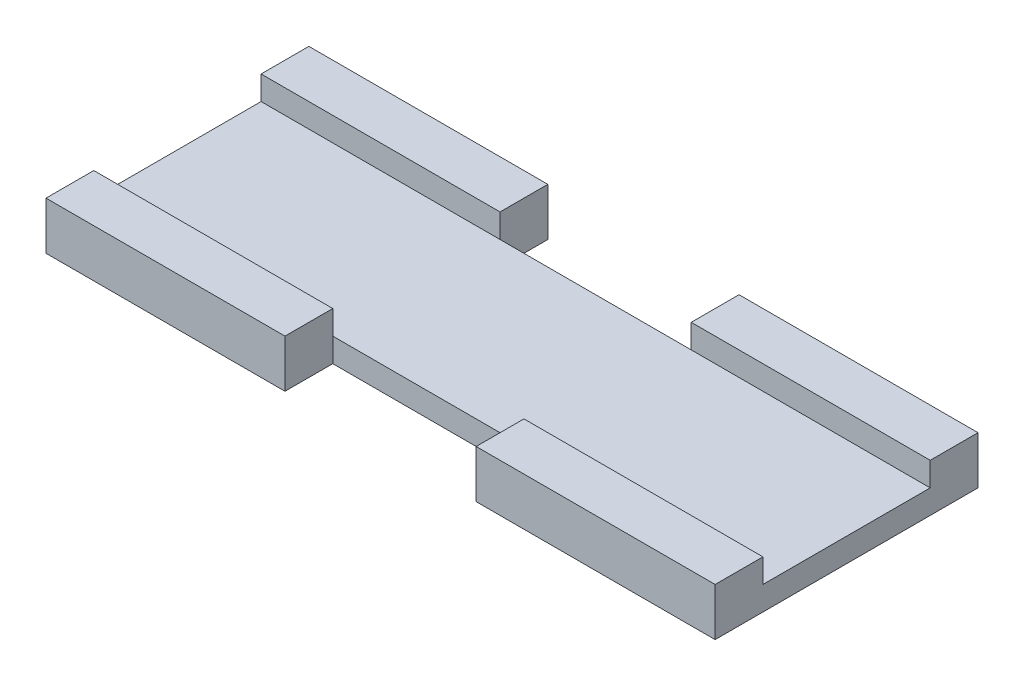
SolidWorks part; units mm, degrees
ref_plane "Спереди" through (0, 0, 0) normal (0, 0, 1) x (1, 0, 0)
ref_plane "Сверху" through (0, 0, 0) normal (0, 1, 0) x (1, 0, 0)
ref_plane "Справа" through (0, 0, 0) normal (1, 0, 0) x (0, 0, -1)
sketch "Эскиз1" plane through (0, 0, 0) normal (0, 1, 0) x (1, 0, 0)
  line L0 (-70, -17.5) -> (-70, 17.5)
  line L1 (70, 17.5) -> (70, -17.5)
  line L2 (-70, 17.5) -> (-70, 27.5)
  line L3 (-70, 27.5) -> (-20, 27.5)
  line L4 (-70, 17.5) -> (70, 17.5)
  line L5 (70, -17.5) -> (-70, -17.5)
  line L6 (-20, 27.5) -> (-20, 17.5)
  line L7 (-20, 17.5) -> (-70, 17.5)
  line L8 (70, 17.5) -> (70, 27.5)
  line L9 (70, 27.5) -> (20, 27.5)
  line L10 (20, 27.5) -> (20, 17.5)
  line L11 (20, 17.5) -> (70, 17.5)
  line L12 (-70, -17.5) -> (-70, -27.5)
  line L13 (-70, -27.5) -> (-20, -27.5)
  line L14 (-20, -27.5) -> (-20, -17.5)
  line L15 (-20, -17.5) -> (-70, -17.5)
  line L16 (70, -17.5) -> (70, -27.5)
  line L17 (70, -27.5) -> (20, -27.5)
  line L18 (20, -27.5) -> (20, -17.5)
  line L19 (20, -17.5) -> (70, -17.5)
extrude "Бобышка-Вытянуть1" add sketch "Эскиз1" along normal blind 5 contours L5 L1 L4 L0 region at (0, 0, 0)
extrude "Бобышка-Вытянуть2" add sketch "Эскиз1<3>" along normal blind 10 contours L6 L3 L2 L4 | L9 L10 L4 L8 | L13 L14 L5 L12 | L18 L17 L16 L5 region at (-45, 0, 22.5) region at (-45, 0, -22.5) region at (45, 0, 22.5) region at (45, 0, -22.5)
sketch "Эскиз1<3>" plane through (0, 0, 0) normal (0, 1, 0) x (1, 0, 0) same geometry as "Эскиз1"
